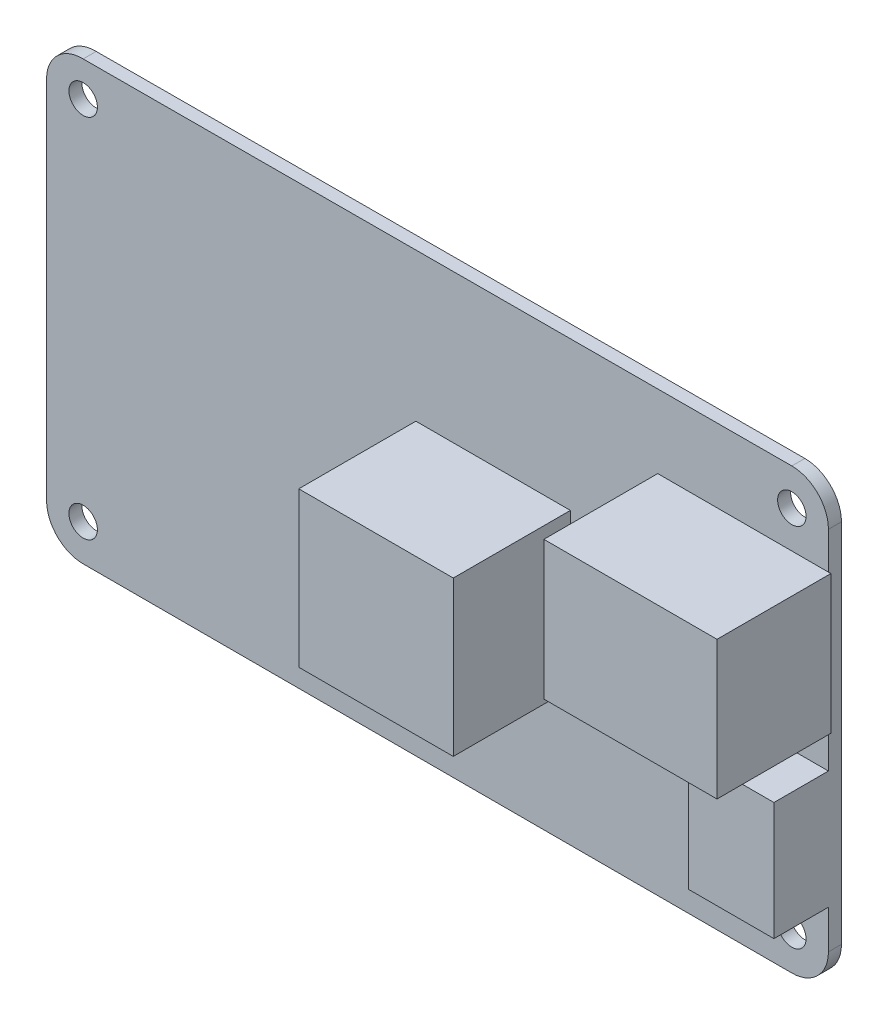
SolidWorks part; units mm, degrees
ref_plane "Front Plane" through (0, 0, 0) normal (0, 0, 1) x (1, 0, 0)
ref_plane "Top Plane" through (0, 0, 0) normal (0, 1, 0) x (1, 0, 0)
ref_plane "Right Plane" through (0, 0, 0) normal (1, 0, 0) x (0, 0, -1)
sketch "pcb" plane through (0, 0, -31.4284) normal (0, 0, 1) x (1, 0, 0)
  line L0 (91.8508, -91.4513) -> (91.8508, -136.4513)
  line L1 (87.3508, -140.9513) -> (0.2108, -140.9513)
  line L2 (-4.2892, -136.4513) -> (-4.2892, -91.4513)
  line L3 (87.3508, -86.9513) -> (0.2108, -87.1809)
  line L4 (-242.3949, -87.1809) -> (70.1051, -87.1809) construction
  circle A0 centre (87.3508, -136.4513) radius 1.75
  circle A1 centre (87.3508, -91.4513) radius 1.75
  circle A2 centre (0.2108, -91.4513) radius 1.75
  circle A3 centre (0.2108, -136.4513) radius 1.75
  arc A4 (87.3508, -140.9513) -> (91.8508, -136.4513) centre (87.3508, -136.4513) ccw
  arc A5 (87.3508, -86.9513) -> (91.8508, -91.4513) centre (87.3508, -91.4513) cw
  circle A6 centre (87.3508, -136.4513) radius 4.5 construction
  arc A7 (91.6807, -137.6771) -> (91.6807, -135.2256) centre (87.3508, -136.4513) ccw construction
  arc A8 (-4.2892, -136.4513) -> (0.2108, -140.9513) centre (0.2108, -136.4513) ccw
  circle A9 centre (0.2108, -136.4513) radius 4.5 construction
  circle A12 centre (87.3508, -91.4513) radius 4.5 construction
  arc A13 (-2.805, -88.1114) -> (3.2266, -88.1114) centre (0.2108, -91.4513) ccw construction
  arc A14 (-4.2892, -91.4513) -> (0.2108, -87.1809) centre (0.096, -91.5661) cw
extrude "board" add sketch "pcb" along normal blind 1.6
sketch "gige" plane through (0, 0, -29.8284) normal (0, 0, 1) x (1, 0, 0)
  line L0 (87.3508, -91.4513) -> (80.434, -91.4513) construction
  line L1 (70.8608, -113.0213) -> (92.1508, -113.0213)
  line L2 (70.8608, -113.0213) -> (70.8608, -96.0113)
  line L3 (70.8608, -96.0113) -> (92.1508, -96.0113)
  line L4 (92.1508, -113.0213) -> (92.1508, -96.0113)
  line L5 (91.8508, -136.4513) -> (91.8508, -91.4513) construction
  dimension "D1" = 4.56
  dimension "D2" = 20.99
  dimension "D3" = 0.3
  dimension "D4" = 17.01
extrude "ethernetport" add sketch "gige" along normal blind 14
sketch "hdmi" plane through (0, 0, -29.8284) normal (0, 0, 1) x (1, 0, 0)
  line L0 (87.3508, -136.4513) -> (81.831, -136.4513) construction
  line L1 (91.8508, -131.6913) -> (81.3508, -131.6913)
  line L2 (91.8508, -131.6913) -> (91.8508, -117.1913)
  line L3 (91.8508, -117.1913) -> (81.3508, -117.1913)
  line L4 (81.3508, -131.6913) -> (81.3508, -117.1913)
  line L5 (91.8508, -136.4513) -> (91.8508, -113.0213) construction
  dimension "D1" = 4.76
  dimension "D2" = 0
  dimension "D3" = 14.5
  dimension "D4" = 10.5
extrude "hdmiport" add sketch "hdmi" along normal blind 6.7
sketch "Sketch9" plane through (0, 0, -29.8284) normal (0, 0, 1) x (1, 0, 0)
  line L0 (91.8508, -117.1913) -> (91.8508, -113.0213) construction
  line L1 (60.1208, -124.3025) -> (41.1208, -124.3025)
  line L2 (60.1208, -124.3025) -> (60.1208, -105.3025)
  line L3 (60.1208, -105.3025) -> (41.1208, -105.3025)
  line L4 (41.1208, -124.3025) -> (41.1208, -105.3025)
  line L5 (93.6051, -141.0625) -> (-250.936, -141.0625) construction
  dimension "D1" = 31.73
  dimension "D2" = 19
  dimension "D3" = 19
  dimension "D4" = 16.76
extrude "FPGAandFan" add sketch "Sketch9" along normal blind 14.4
